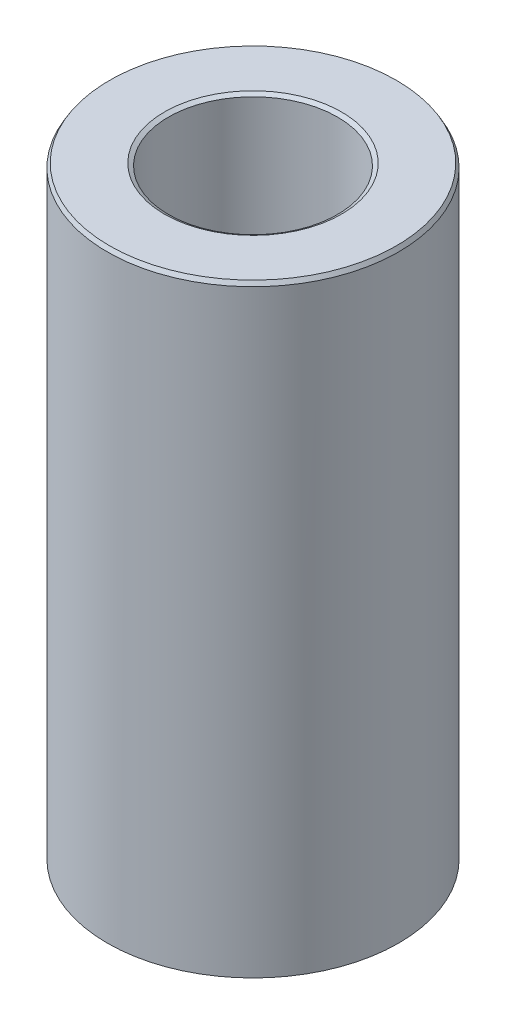
SolidWorks part; units mm, degrees
ref_plane "Front Plane" through (0, 0, 0) normal (0, 0, 1) x (1, 0, 0)
ref_plane "Top Plane" through (0, 0, 0) normal (0, 1, 0) x (1, 0, 0)
ref_plane "Right Plane" through (0, 0, 0) normal (1, 0, 0) x (0, 0, -1)
sketch "Sketch1" plane through (0, 0, 0) normal (0, 1, 0) x (1, 0, 0)
  circle A0 centre (0, 0) radius 40
  dimension "SLEEVE_OD" = 80
extrude "Boss-Extrude1" add sketch "Sketch1" along normal blind 166.0584
sketch "Sketch2" plane through (0, 0, 0) normal (0, 1, 0) x (1, 0, 0)
  circle A0 centre (0, 0) radius 23.1924
  dimension "BORE_D" = 46.3849
extrude "Cut-Extrude1" cut sketch "Sketch2" along normal through all
chamfer "Chamfer1" distance 1.1161 angle 30 4 edges at (0, 166.0584, 23.1924) (0, 0, 23.1924) (0, 0, 40) (0, 166.0584, 40) first distance on face at (0, 166.0584, 23.1924) first distance on face at (0, 0, 23.1924) first distance on face at (0, 166.0584, 40)
